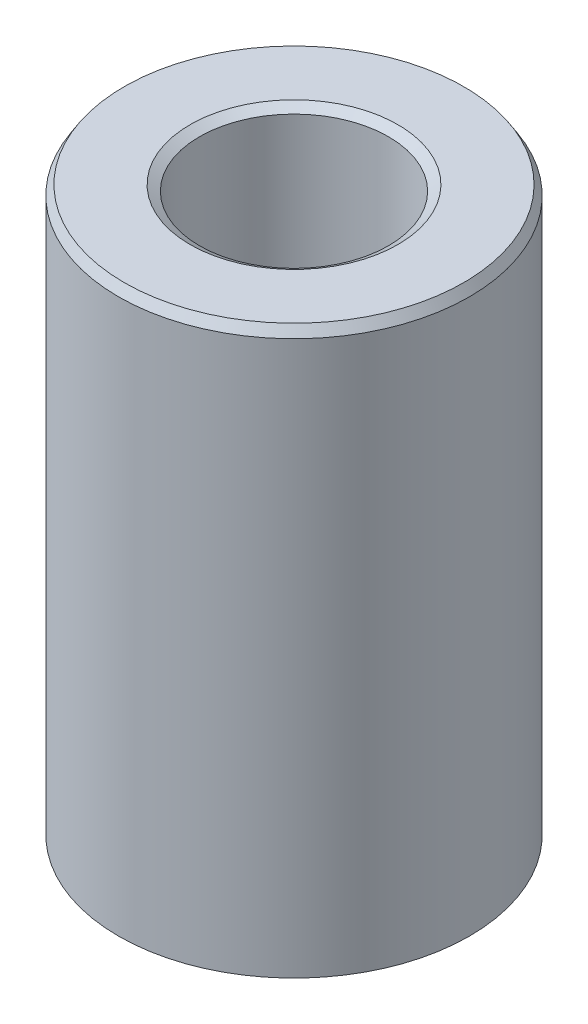
SolidWorks part; units mm, degrees
ref_plane "Front Plane" through (0, 0, 0) normal (0, 0, 1) x (1, 0, 0)
ref_plane "Top Plane" through (0, 0, 0) normal (0, 1, 0) x (1, 0, 0)
ref_plane "Right Plane" through (0, 0, 0) normal (1, 0, 0) x (0, 0, -1)
sketch "Sketch1" plane through (0, 0, 0) normal (0, 1, 0) x (1, 0, 0)
  circle A0 centre (0, 0) radius 42.5
  dimension "SLEEVE_OD" = 85
extrude "Boss-Extrude1" add sketch "Sketch1" along normal blind 137.7456
sketch "Sketch2" plane through (0, 0, 0) normal (0, 1, 0) x (1, 0, 0)
  circle A0 centre (0, 0) radius 22.888
  dimension "BORE_D" = 45.776
extrude "Cut-Extrude1" cut sketch "Sketch2" along normal through all
chamfer "Chamfer1" distance 2.2745 angle 31.406 4 edges at (0, 137.7456, 22.888) (0, 0, 22.888) (0, 0, 42.5) (0, 137.7456, 42.5) first distance on face at (0, 137.7456, 22.888) first distance on face at (0, 0, 22.888) first distance on face at (0, 137.7456, 42.5)
